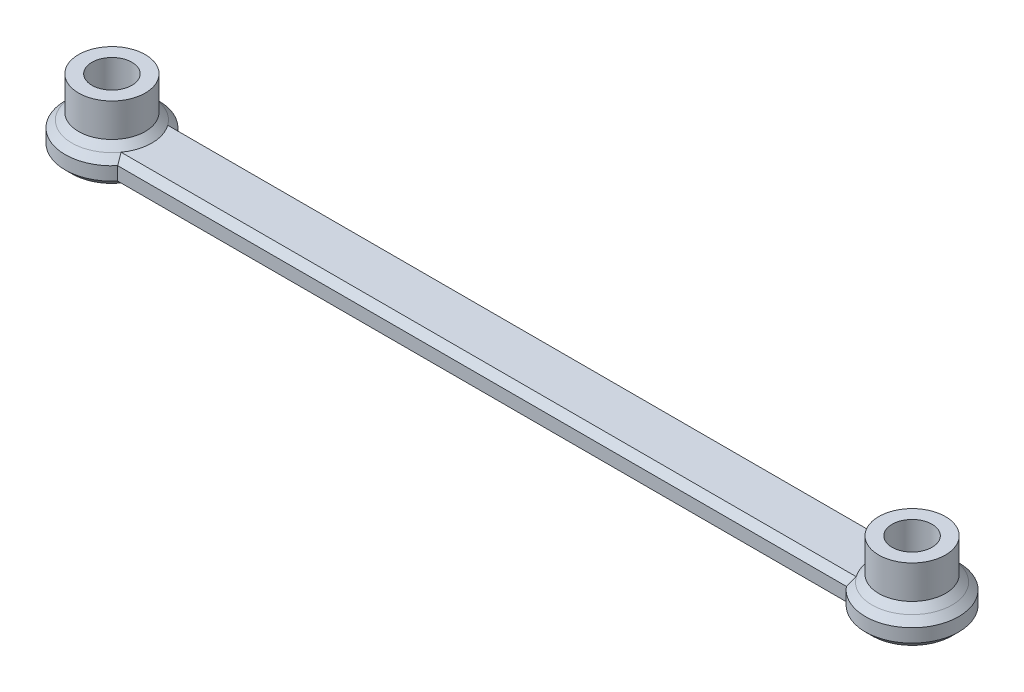
SolidWorks part; units mm, degrees
ref_plane "Front Plane" through (0, 0, 0) normal (0, 0, 1) x (1, 0, 0)
ref_plane "Top Plane" through (0, 0, 0) normal (0, 1, 0) x (1, 0, 0)
ref_plane "Right Plane" through (0, 0, 0) normal (1, 0, 0) x (0, 0, -1)
sketch "Sketch1" plane through (0, 0, 0) normal (0, 1, 0) x (1, 0, 0)
  line L0 (0, 4.5) -> (0, -4.5) construction
  line L1 (54.6381, -4.5) -> (-54.6381, -4.5)
  line L4 (54.6381, 4.5) -> (-54.6381, 4.5)
  line L5 (60, -4.5) -> (-60, 4.5) construction
  line L6 (60, 4.5) -> (-60, -4.5) construction
  circle A0 centre (-60, 0) radius 3
  arc A1 (-54.6381, 4.5) -> (-54.6381, -4.5) centre (-60, 0) ccw
  arc A2 (54.6381, 4.5) -> (54.6381, -4.5) centre (60, 0) cw
  circle A3 centre (60, 0) radius 3
  circle A4 centre (-60, 0) radius 5
  circle A5 centre (60, 0) radius 5
  circle A7 centre (-60, 0) radius 7 construction
  point P0 (0, 0)
  point P20 (-53, 0)
  dimension "D3" = 4
  dimension "D1" = 9
  dimension "D2" = 120
  dimension "D4" = 2
extrude "Boss-Extrude1" add sketch "Sketch1" along normal blind 4 contours A2 L4 A1 L1 A4 A5 region at (0, 0, 0)
extrude "Boss-Extrude2" add sketch "Sketch1<3>" along normal blind 10 contours A4 A0 | A5 A3 region at (-64.8586, 0, 0) region at (55.1414, 0, 0)
sketch "Sketch1<3>" plane through (0, 0, 0) normal (0, 1, 0) x (1, 0, 0) same geometry as "Sketch1"
chamfer "Chamfer1" distance 1 angle 45 2 edges at (60, 4, 5) (-60, 4, 5)
chamfer "Chamfer2" distance 1 angle 45 8 edges at (-67, 0, 0) (0, 0, -4.5) (67, 0, 0) (0, 0, 4.5) (67, 4, 0) (0, 4, -4.5) (-67, 4, 0) (0, 4, 4.5)
